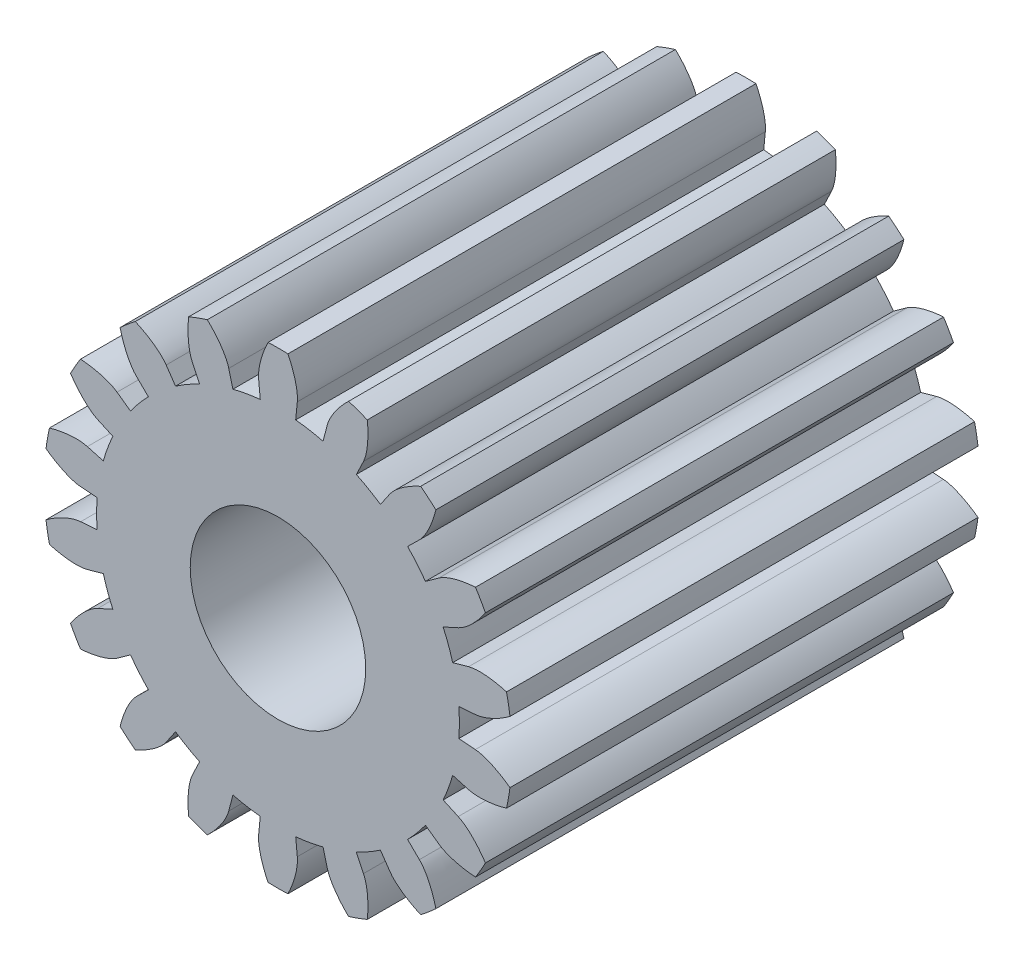
SolidWorks part; units mm, degrees
ref_plane "前视基准面" through (0, 0, 0) normal (0, 0, 1) x (1, 0, 0)
ref_plane "上视基准面" through (0, 0, 0) normal (0, 1, 0) x (1, 0, 0)
ref_plane "右视基准面" through (0, 0, 0) normal (1, 0, 0) x (0, 0, -1)
other "Configuration Table"
sketch "草图1" plane through (0, 0, 0) normal (0, 0, 1) x (1, 0, 0)
  line L0 (0, 0) -> (3.6, 0) construction
  line L1 (0, 0) -> (3.5863, 0.3138) construction
  line L2 (0, 0) -> (3.3729, 0.2594)
  line L3 (3.5863, 0.3138) -> (3.5863, -0.3138) construction
  line L4 (0, 0) -> (3.3729, -0.2594)
  circle A0 centre (0, 0) radius 4
  circle A1 centre (0, 0) radius 3.6 construction
  circle A2 centre (0, 0) radius 3.1
  circle A3 centre (0, 0) radius 3.3829 construction
  circle A4 centre (0, 0) radius 1.5
  spline S0 degree 4 poles (3.3729, 0.2594) (3.3986, 0.2614) (3.47, 0.2722) (3.6019, 0.3141) (3.8043, 0.4106) (4.0445, 0.5752) (4.3197, 0.828) (4.5943, 1.1697) (4.839, 1.5841) (5.0883, 2.1826) (5.2363, 2.8154) (5.2939, 3.4875) (5.2526, 4.2892) (5.1088, 5.0803) (4.8092, 5.9656) (4.3285, 6.8857) (3.7206, 7.7267) (3.0053, 8.4778) (2.2, 9.1312) (1.3219, 9.682) (0.3855, 10.1272) (-0.4709, 10.4234) (-1.2256, 10.6105) (-1.7971, 10.7113) (-2.185, 10.762) (-2.5005, 10.7936) (-2.7712, 10.8122) (-2.9837, 10.8236) (-3.2253, 10.8289) (-3.4702, 10.8308) (-3.7149, 10.8264) (-4.1446, 10.8089) (-4.4935, 10.7735) (-4.8558, 10.7343) (-5.0304, 10.7035) (-5.1473, 10.6866) knots 0 0 0 0 0 0.005604 0.015718 0.02996 0.048734 0.068727 0.096889 0.125051 0.153212 0.209535 0.237696 0.271429 0.327752 0.384075 0.440398 0.496721 0.553044 0.609367 0.66569 0.722013 0.778336 0.806497 0.834659 0.84874 0.86282 0.876901 0.890982 0.900036 0.909091 0.931818 0.954545 0.977273 1 1 1 1 1 construction
  spline S1 degree 4 poles (3.3729, 0.2594) (3.3986, 0.2614) (3.47, 0.2722) (3.6019, 0.3141) (3.8043, 0.4106) (4.0445, 0.5752) (4.3197, 0.828) (4.5943, 1.1697) (4.839, 1.5841) (5.0883, 2.1826) (5.2363, 2.8154) (5.2939, 3.4875) (5.2526, 4.2892) (5.1088, 5.0803) (4.8092, 5.9656) (4.3285, 6.8857) (3.7206, 7.7267) (3.0053, 8.4778) (2.2, 9.1312) (1.3219, 9.682) (0.3855, 10.1272) (-0.4709, 10.4234) (-1.2256, 10.6105) (-1.7971, 10.7113) (-2.185, 10.762) (-2.5005, 10.7936) (-2.7712, 10.8122) (-2.9837, 10.8236) (-3.2253, 10.8289) (-3.3689, 10.83) (-3.4447, 10.8298) (-3.4825, 10.8294) knots 0 0 0 0 0 0.005604 0.015718 0.02996 0.048734 0.068727 0.096889 0.125051 0.153212 0.209535 0.237696 0.271429 0.327752 0.384075 0.440398 0.496721 0.553044 0.609367 0.66569 0.722013 0.778336 0.806497 0.834659 0.84874 0.86282 0.876901 0.890982 0.900036 0.909091 0.909091 0.909091 0.909091 0.909091
  spline S2 degree 4 poles (3.3729, -0.2594) (3.3986, -0.2614) (3.47, -0.2722) (3.6019, -0.3141) (3.8043, -0.4106) (4.0445, -0.5752) (4.3197, -0.828) (4.5943, -1.1697) (4.839, -1.5841) (5.0883, -2.1826) (5.2363, -2.8154) (5.2939, -3.4875) (5.2526, -4.2892) (5.1088, -5.0803) (4.8092, -5.9656) (4.3285, -6.8857) (3.7206, -7.7267) (3.0053, -8.4778) (2.2, -9.1312) (1.3219, -9.682) (0.3855, -10.1272) (-0.4709, -10.4234) (-1.2256, -10.6105) (-1.7971, -10.7113) (-2.185, -10.762) (-2.5005, -10.7936) (-2.7712, -10.8122) (-2.9837, -10.8236) (-3.2253, -10.8289) (-3.4702, -10.8308) (-3.7149, -10.8264) (-4.1446, -10.8089) (-4.4935, -10.7735) (-4.8558, -10.7343) (-5.0304, -10.7035) (-5.1473, -10.6866) knots 0 0 0 0 0 0.005604 0.015718 0.02996 0.048734 0.068727 0.096889 0.125051 0.153212 0.209535 0.237696 0.271429 0.327752 0.384075 0.440398 0.496721 0.553044 0.609367 0.66569 0.722013 0.778336 0.806497 0.834659 0.84874 0.86282 0.876901 0.890982 0.900036 0.909091 0.931818 0.954545 0.977273 1 1 1 1 1 construction
  spline S3 degree 4 poles (3.3729, -0.2594) (3.3986, -0.2614) (3.47, -0.2722) (3.6019, -0.3141) (3.8043, -0.4106) (4.0445, -0.5752) (4.3197, -0.828) (4.5943, -1.1697) (4.839, -1.5841) (5.0883, -2.1826) (5.2363, -2.8154) (5.2939, -3.4875) (5.2526, -4.2892) (5.1088, -5.0803) (4.8092, -5.9656) (4.3285, -6.8857) (3.7206, -7.7267) (3.0053, -8.4778) (2.2, -9.1312) (1.3219, -9.682) (0.3855, -10.1272) (-0.4709, -10.4234) (-1.2256, -10.6105) (-1.7971, -10.7113) (-2.185, -10.762) (-2.5005, -10.7936) (-2.7712, -10.8122) (-2.9837, -10.8236) (-3.2253, -10.8289) (-3.3689, -10.83) (-3.4447, -10.8298) (-3.4825, -10.8294) knots 0 0 0 0 0 0.005604 0.015718 0.02996 0.048734 0.068727 0.096889 0.125051 0.153212 0.209535 0.237696 0.271429 0.327752 0.384075 0.440398 0.496721 0.553044 0.609367 0.66569 0.722013 0.778336 0.806497 0.834659 0.84874 0.86282 0.876901 0.890982 0.900036 0.909091 0.909091 0.909091 0.909091 0.909091
  point P15 (3.5863, 0)
  dimension "齿顶圆直径" = 8
  dimension "分度圆直径" = 7.2
  dimension "齿根圆直径" = 6.2
  dimension "基圆直径" = 6.7658
  dimension "内孔直径" = 3
  dimension "渐近线镜像线夹角" = 5
extrude "凸台-拉伸1" add sketch "草图1" along normal blind 8 contours A0 | A4
extrude "切除-拉伸1" cut sketch "草图1<3>" along normal through all contours A2 S3 A0 S1 region at (3.6085, 0, 0)
sketch "草图1<3>" plane through (0, 0, 0) normal (0, 0, 1) x (1, 0, 0) same geometry as "草图1"
pattern_circular "阵列(圆周)1" count 18 every 20 about axis through (0, 0, 8) along (0, 0, 1) of "切除-拉伸1"
equation "\"m\"= 0.4'模数"
equation "\"z\" = 18'齿数"
equation "\"a\"= 20度'压力角"
equation "\"d\"= \"m\" * \"z\"'分度圆直径"
equation "\"da\"= ( \"z\" + 2 ) * \"m\"'齿顶圆直径"
equation "\"df\"= ( \"z\" - 2.5 ) * \"m\"'齿根圆直径"
equation "\"s\"= 0.5 * PI * \"m\"'分度圆齿厚"
equation "\"r\"= 0.38 * \"m\"'齿根圆角"
equation "\"B\"= 0.3 * \"d\"'齿厚"
equation "\"db\"= \"m\" * \"z\" * cos ( \"a\" )'基圆直径"
equation "\"rb\"= \"db\" / 2'基圆半径"
equation "\"齿顶圆直径@草图1\"= \"da\""
equation "\"分度圆直径@草图1\"= \"d\""
equation "\"齿根圆直径@草图1\"= \"df\""
equation "\"基圆直径@草图1\"= \"db\""
equation "\"渐近线镜像线夹角@草图1\"= 360 / 4 / \"z\""
equation "\"h\"= 8'齿轮厚度"
equation "\"ir\"= 3'内孔直径"
equation "\"内孔直径@草图1\"= \"ir\""
equation "\"齿轮厚@凸台-拉伸1\"= \"h\""
equation "\"齿轮夹角@阵列(圆周)1\"= 360 / \"z\""
equation "\"齿数@阵列(圆周)1\"= \"z\""
